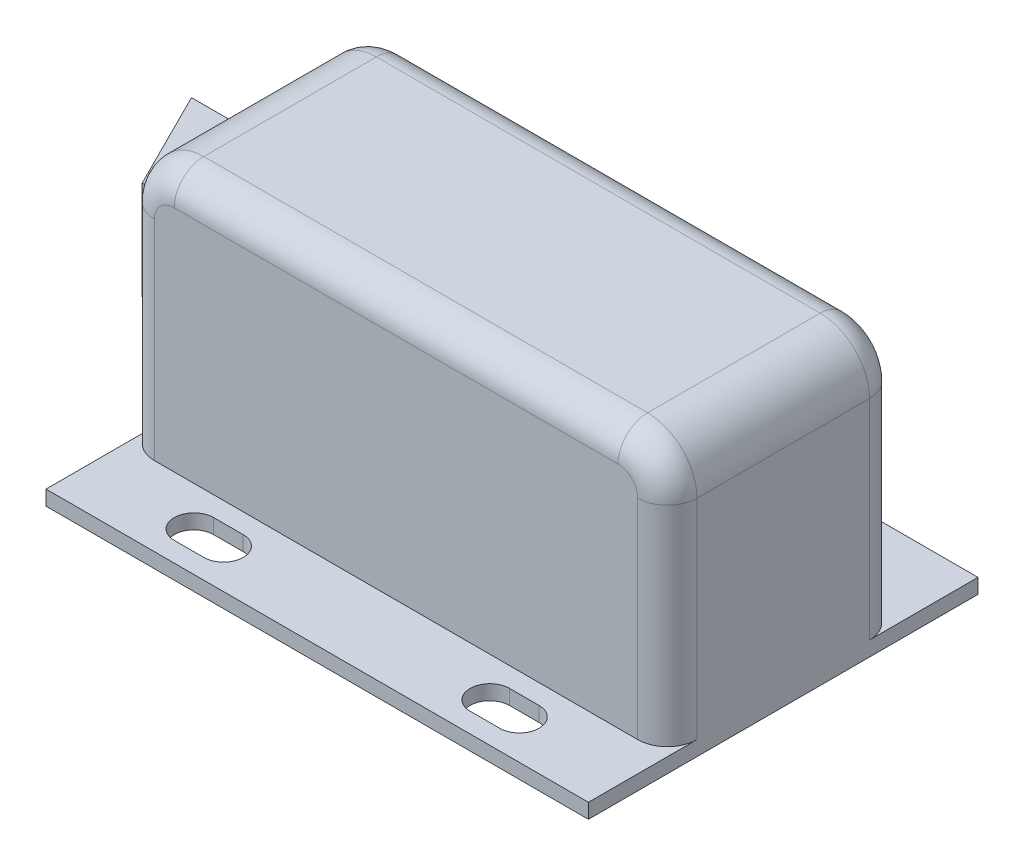
SolidWorks part; units mm, degrees
ref_plane "Front Plane" through (0, 0, 0) normal (0, 0, 1) x (1, 0, 0)
ref_plane "Top Plane" through (0, 0, 0) normal (0, 1, 0) x (1, 0, 0)
ref_plane "Right Plane" through (0, 0, 0) normal (1, 0, 0) x (0, 0, -1)
ref_plane "Plane1" through (0, 13.85, 0) normal (0, 1, 0) x (1, 0, 0)
sketch "Sketch1" plane through (0, 13.85, 0) normal (0, 1, 0) x (1, 0, 0)
  line L0 (-27.5, 8) -> (-27.5, -31.5)
  line L1 (-27.5, -31.5) -> (27.5, -31.5)
  line L2 (27.5, -31.5) -> (27.5, 8)
  line L3 (27.5, 8) -> (-27.5, 8)
extrude "Boss-Extrude1" add sketch "Sketch1" against normal blind 27.7
sketch "Sketch2" plane through (-27.5, 0, 0) normal (-1, 0, 0) x (0, 0, 1)
  line L0 (31.5, 13.85) -> (23.5, 13.85)
  line L1 (23.5, 13.85) -> (23.5, -12.35)
  line L2 (23.5, -12.35) -> (31.5, -12.35)
  line L3 (31.5, -12.35) -> (31.5, 13.85)
extrude "Cut-Extrude1" cut sketch "Sketch2" against normal through all
sketch "Sketch3" plane through (-27.5, 0, 0) normal (-1, 0, 0) x (0, 0, 1)
  line L0 (0, -12.35) -> (0, 13.85)
  line L1 (0, 13.85) -> (-8, 13.85)
  line L2 (-8, 13.85) -> (-8, -12.35)
  line L3 (-8, -12.35) -> (0, -12.35)
extrude "Cut-Extrude2" cut sketch "Sketch3" against normal through all
sketch "Sketch4" plane through (0, -12.35, 0) normal (0, 1, 0) x (-1, 0, 0)
  line L0 (-13.5, -2) -> (-16.5, -2)
  line L1 (-16.5, -6) -> (-13.5, -6)
  arc A0 (-16.5, -2) -> (-16.5, -6) centre (-16.5, -4) ccw
  arc A1 (-13.5, -6) -> (-13.5, -2) centre (-13.5, -4) ccw
extrude "Cut-Extrude3" cut sketch "Sketch4" against normal through all
sketch "Sketch5" plane through (0, -13.85, 0) normal (0, -1, 0) x (1, 0, 0)
  line L0 (-16.5, -6) -> (-13.5, -6)
  line L1 (-13.5, -2) -> (-16.5, -2)
  arc A0 (-13.5, -6) -> (-13.5, -2) centre (-13.5, -4) ccw
  arc A1 (-16.5, -2) -> (-16.5, -6) centre (-16.5, -4) ccw
extrude "Cut-Extrude4" cut sketch "Sketch5" against normal through all
sketch "Sketch6" plane through (0, -12.35, 0) normal (0, 1, 0) x (-1, 0, 0)
  line L0 (16.5, 29.5) -> (13.5, 29.5)
  line L1 (13.5, 25.5) -> (16.5, 25.5)
  arc A0 (13.5, 29.5) -> (13.5, 25.5) centre (13.5, 27.5) ccw
  arc A1 (16.5, 25.5) -> (16.5, 29.5) centre (16.5, 27.5) ccw
extrude "Cut-Extrude5" cut sketch "Sketch6" against normal through all
sketch "Sketch7" plane through (0, -13.85, 0) normal (0, -1, 0) x (1, 0, 0)
  line L0 (13.5, 25.5) -> (16.5, 25.5)
  line L1 (16.5, 29.5) -> (13.5, 29.5)
  arc A0 (16.5, 25.5) -> (16.5, 29.5) centre (16.5, 27.5) ccw
  arc A1 (13.5, 29.5) -> (13.5, 25.5) centre (13.5, 27.5) ccw
extrude "Cut-Extrude6" cut sketch "Sketch7" against normal through all
ref_plane "Plane2" through (0, -5.35, 0) normal (0, -1, 0) x (1, 0, 0)
sketch "Sketch8" plane through (0, -5.35, 0) normal (0, -1, 0) x (1, 0, 0)
  line L0 (-32.5, 16.75) -> (-37.5, 6.75)
  line L1 (-37.5, 6.75) -> (-27.5, 6.75)
  line L2 (-27.5, 6.75) -> (-27.5, 16.75)
  line L3 (-27.5, 16.75) -> (-32.5, 16.75)
extrude "Boss-Extrude2" add sketch "Sketch8" against normal blind 10
fillet "Fillet1" radius 5 2 edges at (27.5, 13.85, 11.75) (-27.5, 13.85, 11.75) tangent propagation no
fillet "Fillet2" radius 3 10 edges at (27.5, -1.75, 23.5) (26.0355, 12.3855, 23.5) (0, 13.85, 23.5) (-26.0355, 12.3855, 23.5) (-27.5, -1.75, 23.5) (-27.5, -1.75, 0) (-26.0355, 12.3855, 0) (0, 13.85, 0) (26.0355, 12.3855, 0) (27.5, -1.75, 0) tangent propagation no
